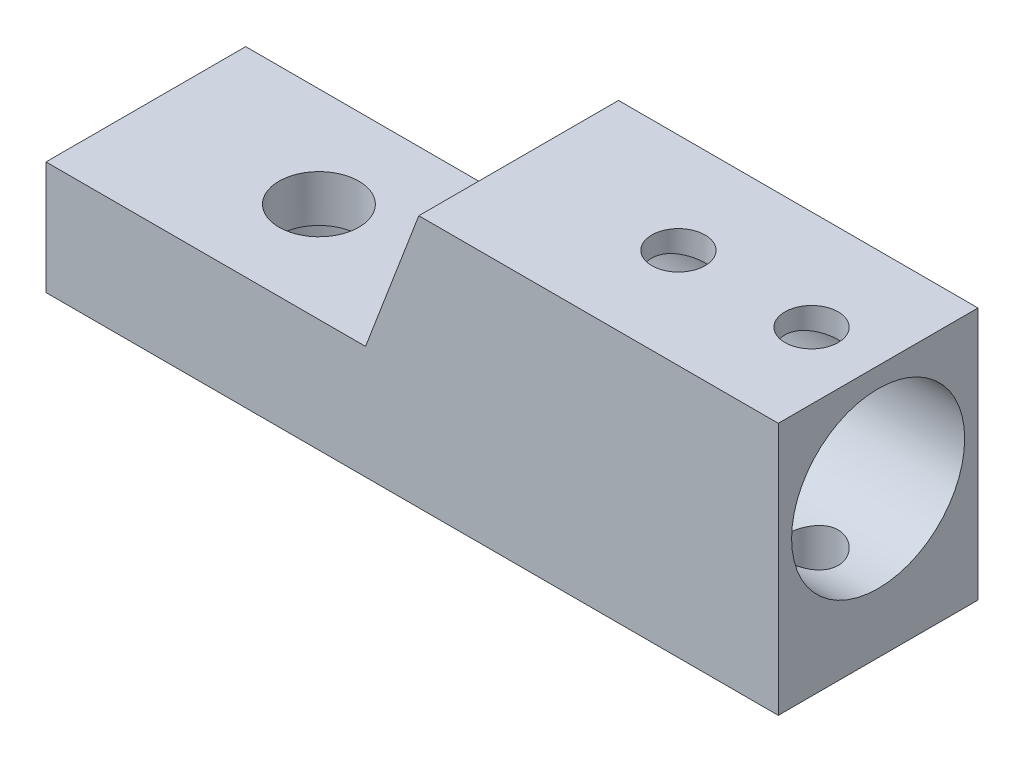
SolidWorks part; units mm, degrees
ref_plane "Front Plane" through (0, 0, 0) normal (0, 0, 1) x (1, 0, 0)
ref_plane "Top Plane" through (0, 0, 0) normal (0, 1, 0) x (1, 0, 0)
ref_plane "Right Plane" through (0, 0, 0) normal (1, 0, 0) x (0, 0, -1)
sketch "Sketch8" plane through (0, 0, 0) normal (1, 0, 0) x (0, 0, -1)
  line L1 (-6.5, -11) -> (6.5, -11)
  line L2 (-6.5, -11) -> (-6.5, 6.5)
  line L3 (-6.5, 6.5) -> (6.5, 6.5)
  line L4 (6.5, -11) -> (6.5, 6.5)
  circle A0 centre (0, 0) radius 6.5
sketch "Sketch1" plane through (0, 0, 0) normal (1, 0, 0) x (0, 0, -1)
  line L4 (7.5, -11) -> (7.5, 8)
  line L5 (-7.5, 8) -> (7.5, 8)
  line L6 (-7.5, -11) -> (7.5, -11)
  line L7 (-7.5, -11) -> (-7.5, 8)
  circle A1 centre (0, 0) radius 6.5
  point P7 (0, -11)
  dimension "D1" = 15
  dimension "D2" = 19
  dimension "D3" = 13
extrude "Boss-Extrude1" add sketch "Sketch1" along normal blind 25 contours A1 L7 L6 L4 | A1 L5 L7 | A1 L4 L5 region at (0, -10.7579, 0)
sketch "Sketch2" plane through (0, 0, 0) normal (1, 0, 0) x (0, 0, -1)
  line L8 (7.5, 8) -> (-7.5, 8)
  line L13 (7.5, 8) -> (7.5, -11)
  line L14 (7.5, -11) -> (-7.5, -11)
  line L15 (-7.5, 8) -> (-7.5, -11)
  point P0 (0, 0)
extrude "Boss-Extrude2" add sketch "Sketch2" against normal blind 2
ref_plane "Plane1" through (0, -2.5, 0) normal (0, 1, 0) x (1, 0, 0)
sketch "Sketch3" plane through (0, -2.5, 0) normal (0, 1, 0) x (1, 0, 0)
  line L0 (-30, -7.5) -> (-30, 7.5)
  line L1 (-2, -7.5) -> (-2, 7.5)
  line L11 (-30, -7.5) -> (-2, -7.5)
  line L13 (-30, 7.5) -> (-2, 7.5)
  circle A3 centre (-17, 0) radius 3
  point P2 (-9.5853, 0)
  dimension "D2" = 7.5
  dimension "D3" = 6
  dimension "D4" = 28
  dimension "D1" = 7.5
  dimension "D5" = 2
  dimension "D6" = 17
sketch "Sketch4" plane through (0, 0, 0) normal (0, 1, 0) x (1, 0, 0)
  line L0 (25, -7.5) -> (25, 7.5) construction
  circle A0 centre (10, 0) radius 2
  circle A1 centre (20, 0) radius 2
  dimension "D1" = 4
  dimension "D2" = 5
  dimension "D3" = 10
extrude "Cut-Extrude1" cut sketch "Sketch4" against normal through all both and the other way through all
extrude "Boss-Extrude3" add sketch "Sketch3" against normal blind 8.5
sketch "Sketch5" plane through (0, -11, 0) normal (0, -1, 0) x (1, 0, 0)
  circle A0 centre (-17, 0) radius 5
  dimension "D1" = 10
extrude "Cut-Extrude2" [suppressed] cut sketch "Sketch5" against normal blind 3
chamfer "Chamfer1" distance 10.5 distance2 4 1 edges at (-2, -2.5, 0) first distance on face at (-2, 2.75, 0)
sketch "Sketch7" plane through (0, -11, 0) normal (0, -1, 0) x (1, 0, 0)
  circle A2 centre (-17, 0) radius 6
  dimension "D1" = 12
extrude "Cut-Extrude4" cut sketch "Sketch7" against normal blind 5
